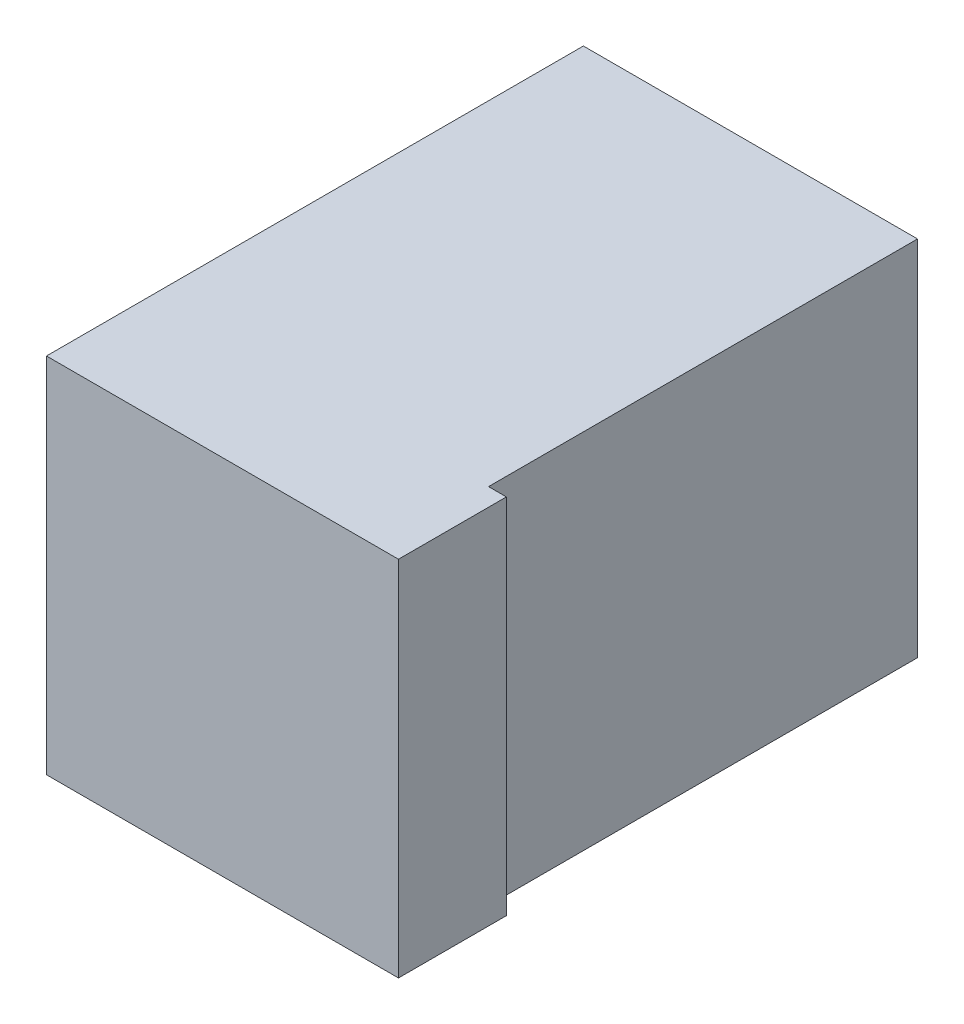
SolidWorks part; units mm, degrees
material "Copper"
ref_plane "Front Plane" through (0, 0, 0) normal (0, 0, 1) x (1, 0, 0)
ref_plane "Top Plane" through (0, 0, 0) normal (0, 1, 0) x (1, 0, 0)
ref_plane "Right Plane" through (0, 0, 0) normal (1, 0, 0) x (0, 0, -1)
sketch "Sketch1" plane through (0, 0, 0) normal (0, 0, 1) x (1, 0, 0)
  line L1 (0, 0) -> (-99, 0)
  line L2 (0, 0) -> (0, -102)
  line L3 (0, -102) -> (-99, -102)
  line L4 (-99, 0) -> (-99, -102)
  dimension "D1" = 99
  dimension "D2" = 102
extrude "Boss-Extrude1" add sketch "Sketch1" along normal blind 151
sketch "Sketch3" plane through (0, -102, 0) normal (0, -1, 0) x (1, 0, 0)
  line L0 (-99, 151) -> (-99, 0) construction
  line L1 (0, 0) -> (-5.02, 0)
  line L2 (0, 0) -> (0, 120.65)
  line L3 (0, 120.65) -> (-5.02, 120.65)
  line L4 (-5.02, 0) -> (-5.02, 120.65)
  dimension "D1" = 120.65
  dimension "D2" = 93.98
extrude "Cut-Extrude2" cut sketch "Sketch3" against normal blind 152.4
